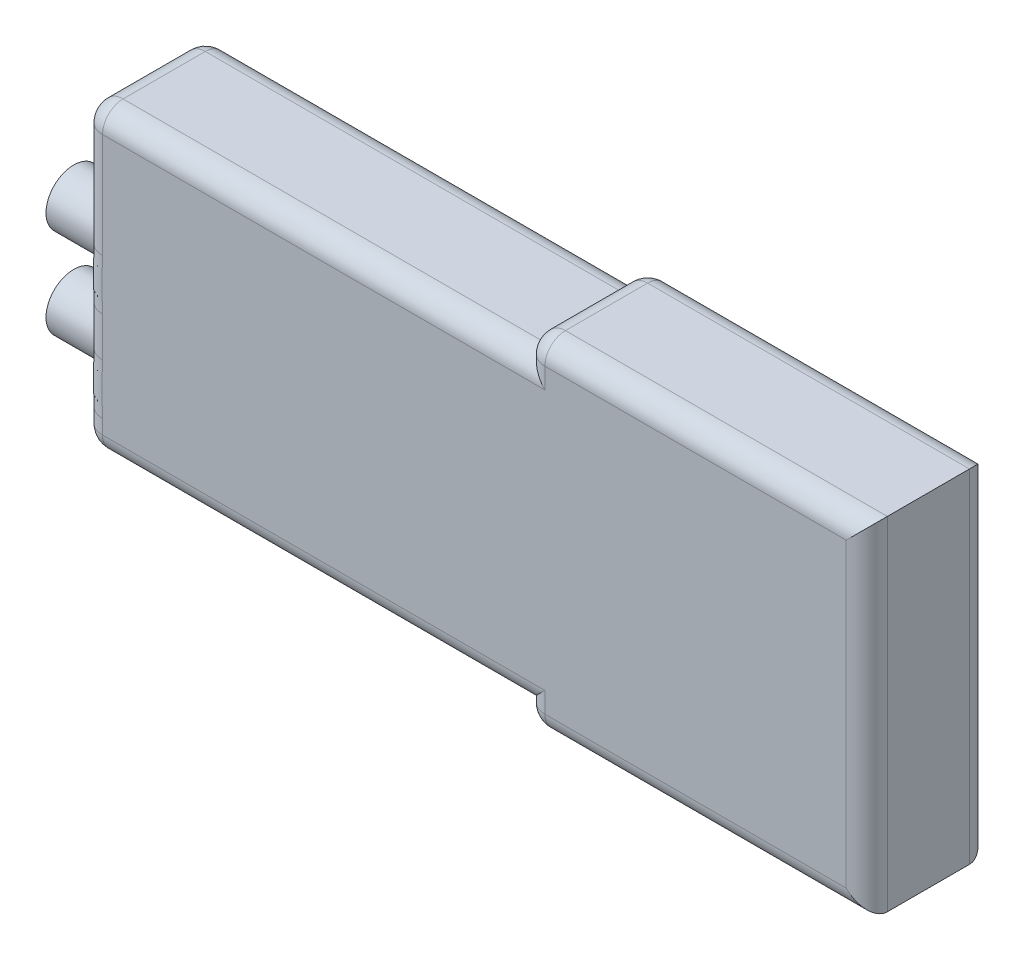
SolidWorks part; units mm, degrees
ref_plane "Front Plane" through (0, 0, 0) normal (0, 0, 1) x (1, 0, 0)
ref_plane "Top Plane" through (0, 0, 0) normal (0, 1, 0) x (1, 0, 0)
ref_plane "Right Plane" through (0, 0, 0) normal (1, 0, 0) x (0, 0, -1)
sketch "Sketch1" plane through (0, 0, 0) normal (0, 0, 1) x (1, 0, 0)
  line L1 (4.1658, -4.1658) -> (-4.1658, -4.1658)
  line L2 (4.1658, -4.1658) -> (4.1658, 4.1658)
  line L3 (4.1658, 4.1658) -> (-4.1658, 4.1658)
  line L4 (-4.1658, -4.1658) -> (-4.1658, 4.1658)
  line L5 (4.1658, -4.1658) -> (-4.1658, 4.1658) construction
  line L6 (4.1658, 4.1658) -> (-4.1658, -4.1658) construction
  point P0 (0, 0)
  dimension "D1" = 8.3316
extrude "Boss-Extrude1" add sketch "Sketch1" along normal blind 3
sketch "Sketch2" plane through (-4.1658, 0, 0) normal (-1, 0, 0) x (0, 0, 1)
  line L1 (0, 3.6658) -> (3, 3.6658)
  line L2 (0, 3.6658) -> (0, -3.6658)
  line L3 (0, -3.6658) -> (3, -3.6658)
  line L4 (3, 3.6658) -> (3, -3.6658)
  point P6 (0, 0)
  point P7 (0, 0)
extrude "Boss-Extrude2" add sketch "Sketch2" along normal blind 10.7621
sketch "Sketch3" plane through (-14.9279, 0, 0) normal (-1, 0, 0) x (0, 0, 1)
  line L0 (0, 3.6658) -> (1.5, 2.2) construction
  line L1 (1.5, 2.2) -> (3, 3.6658) construction
  line L2 (1.5, 2.2) -> (1.5, 3.6658) construction
  line L3 (3, 3.6658) -> (0, 3.6658) construction
  line L4 (1.5, -2.2) -> (1.5, -3.6658) construction
  circle A0 centre (1.5, 2.2) radius 0.675 construction
  circle A1 centre (1.5, 0) radius 0.675
  circle A2 centre (1.5, -2.2) radius 0.675
  point P8 (0, 0)
  point P15 (0, 0)
  dimension "D1" = 1.35
  dimension "D2" = 2.2
  dimension "D3" = 2.2
extrude "Boss-Extrude3" add sketch "Sketch3" along normal blind 1.7
fillet "Fillet2" radius 0.5 2 edges at (-14.9279, -2.2, 2.175) (-14.9279, 0, 2.175)
fillet "Fillet3" radius 0.5 18 edges at (-14.9279, 0, 3) (-14.9279, 0, 0) (-9.5469, -3.6658, 3) (-9.5469, -3.6658, 0) (-9.5469, 3.6658, 0) (-9.5469, 3.6658, 3) (-14.9279, -3.6658, 1.5) (-14.9279, 3.6658, 1.5) (0, 4.1658, 3) (4.1658, 0, 3) (0, -4.1658, 3) (-4.1658, -3.9158, 3) (-4.1658, 3.9158, 3) (4.1658, 0, 0) (0, -4.1658, 0) (-4.1658, -3.9158, 0) (0, 4.1658, 0) (-4.1658, 3.9158, 0)
fillet "Fillet4" radius 0.5 6 edges at (-4.0194, -4.0194, 2.8536) (-4.0194, -4.0194, 0.1464) (-4.0194, 4.0194, 2.8536) (-4.0194, 4.0194, 0.1464) (-4.1658, -4.1658, 1.5) (-4.1658, 4.1658, 1.5)
